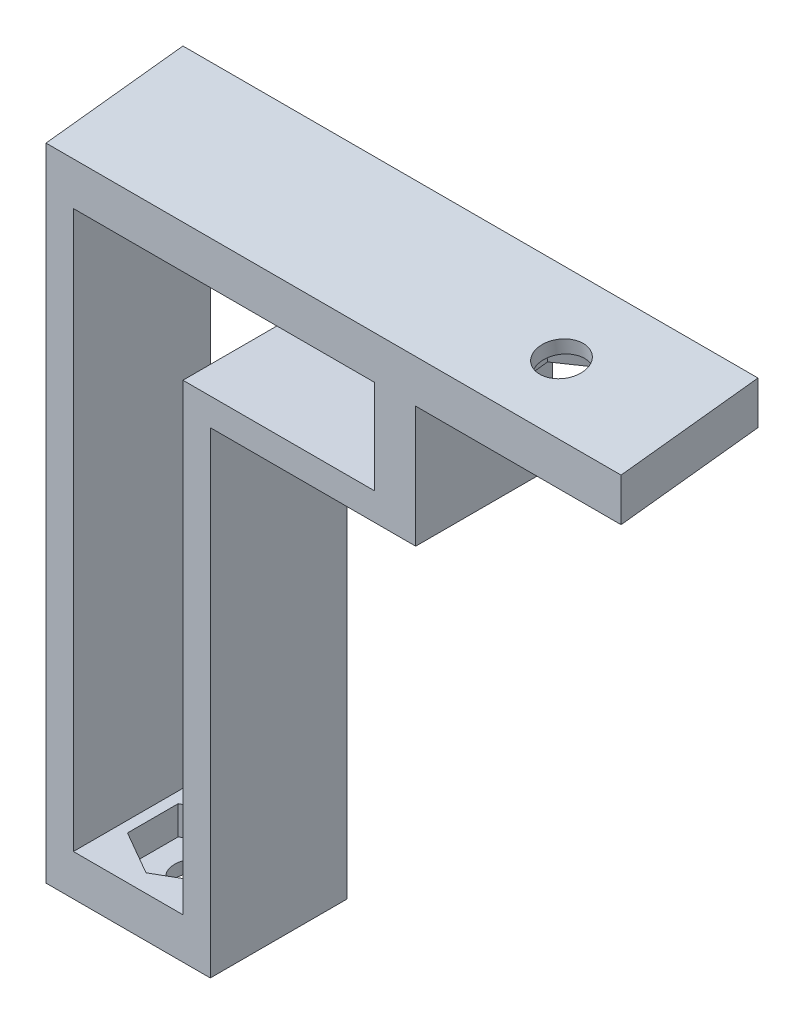
SolidWorks part; units mm, degrees
note: The reader was unsure of these and kept them because the rebuilt part matched: shared geometry of "Sketch3<2>", "Sketch4<4>".
ref_plane "Front Plane" through (0, 0, 0) normal (0, 0, 1) x (1, 0, 0)
ref_plane "Top Plane" through (0, 0, 0) normal (0, 1, 0) x (1, 0, 0)
ref_plane "Right Plane" through (0, 0, 0) normal (1, 0, 0) x (0, 0, -1)
sketch "Sketch1" plane through (0, 0, 0) normal (0, 0, 1) x (1, 0, 0)
  line L0 (0, 0) -> (0, 34.81)
  line L1 (0, 34.81) -> (30, 34.81)
  line L2 (30, 34.81) -> (30, 46.81)
  line L3 (30, 46.81) -> (-12, 46.81)
  line L4 (-12, 46.81) -> (-12, 0)
  line L5 (-12, 0) -> (0, 0)
  line L6 (-2, 3) -> (-2, 36.81)
  line L7 (-2, 36.81) -> (27, 36.81)
  line L8 (27, 36.81) -> (27, 44.81)
  line L9 (27, 44.81) -> (-10, 44.81)
  line L10 (-10, 44.81) -> (-10, 3)
  line L11 (-10, 3) -> (-2, 3)
  line L12 (-10, 44.81) -> (-12, 44.81)
  line L13 (27, 44.81) -> (30, 44.81)
  line L14 (12, 44.81) -> (12, 36.81)
  line L15 (15, 44.81) -> (15, 36.81)
  line L16 (15, 36.81) -> (15, 34.81)
  dimension "D2" = 2
  dimension "D3" = 3
  dimension "D4" = 2
  dimension "D5" = 2
  dimension "D6" = 2
  dimension "D7" = 3
  dimension "D8" = 8
  dimension "D9" = 8
  dimension "D10" = 30
  dimension "D11" = 44.81
  dimension "D12" = 3
  dimension "D13" = 15
extrude "Boss-Extrude1" add sketch "Sketch1" against normal blind 10 contours L13 L8 L7 L6 L11 L10 L12 L4 L5 L0 L1 L2 | L15 L9 L14 L7 | L9 L13 L2 L3 L4 L12
sketch "Sketch2" plane through (30, 0, 0) normal (1, 0, 0) x (0, 0, -1)
  line L0 (0, 46.81) -> (10, 47.9494)
  line L1 (10, 47.9494) -> (10, 46.81)
  line L2 (10, 46.81) -> (10, 44.81) construction
  line L3 (10, 44.81) -> (0, 44.81) construction
  line L4 (0, 43.6706) -> (10, 44.81)
  line L5 (0, 46.81) -> (0, 44.81) construction
  line L6 (0, 43.6706) -> (0, 44.81)
  line L7 (0, 44.81) -> (0, 46.81)
  point P13 (0, 0)
  dimension "D1" = 6.5
extrude "Boss-Extrude2" add sketch "Sketch2" against normal up to surface (42 mm away) up to face at (-12, 23.405, -5)
sketch "Sketch3" plane through (0, 43.111, 4.9119) normal (0, -0.9936, -0.1132) x (1, 0, 0)
  line L0 (30, -9.976) -> (-10, -9.976) construction
  line L5 (24.2, -8.1285) -> (21, -6.281)
  line L6 (21, -6.281) -> (17.8, -8.1285)
  line L7 (17.8, -8.1285) -> (17.8, -11.8235)
  line L8 (17.8, -11.8235) -> (21, -13.671)
  line L9 (21, -13.671) -> (24.2, -11.8235)
  line L10 (24.2, -11.8235) -> (24.2, -8.1285)
  line L12 (30, -4.9437) -> (30, -15.0084) construction
  line L14 (-10, -15.0084) -> (-10, -4.9437) construction
  circle A0 centre (21, -9.976) radius 3.2 construction
  circle A1 centre (21, -9.976) radius 1.6
  point P2 (0, 0)
  point P3 (0, 0)
  point P7 (21, -9.976)
  point P16 (0, 0)
  point P17 (17.8, -11.8235)
  point P18 (30, -9.976)
  point P19 (0, 0)
  point P22 (0, 0)
  point P23 (0, 0)
  point P24 (0, 0)
  dimension "D1" = 6.4
  dimension "D2" = 3.2
  dimension "D3" = 9
extrude "Cut-Extrude1" cut sketch "Sketch3" against normal blind 2.1
extrude "Cut-Extrude2" cut sketch "Sketch3<2>" against normal through all contours A1
sketch "Sketch3<2>" plane through (0, 43.111, 4.9119) normal (0, -0.9936, -0.1132) x (1, 0, 0) same geometry as "Sketch3"
sketch "Sketch4" plane through (0, 3, 0) normal (0, 1, 0) x (1, 0, 0)
  line L0 (-2, 5) -> (-10, 5) construction
  line L1 (-2, 10) -> (-2, 0) construction
  line L2 (-10, 10) -> (-10, 0) construction
  line L4 (-2.8, 3.1525) -> (-2.8, 6.8475)
  line L5 (-2.8, 6.8475) -> (-6, 8.695)
  line L6 (-6, 8.695) -> (-9.2, 6.8475)
  line L7 (-9.2, 6.8475) -> (-9.2, 3.1525)
  line L8 (-9.2, 3.1525) -> (-6, 1.305)
  line L9 (-6, 1.305) -> (-2.8, 3.1525)
  circle A0 centre (-6, 5) radius 3.2 construction
  circle A1 centre (-6, 5) radius 1.6
  point P6 (-6, 5)
  dimension "D1" = 3.2
  dimension "D2" = 6.4
extrude "Cut-Extrude3" cut sketch "Sketch4" against normal blind 2.1
extrude "Cut-Extrude4" cut sketch "Sketch4<4>" against normal through all contours A1
sketch "Sketch4<4>" plane through (0, 3, 0) normal (0, 1, 0) x (1, 0, 0) same geometry as "Sketch4"
